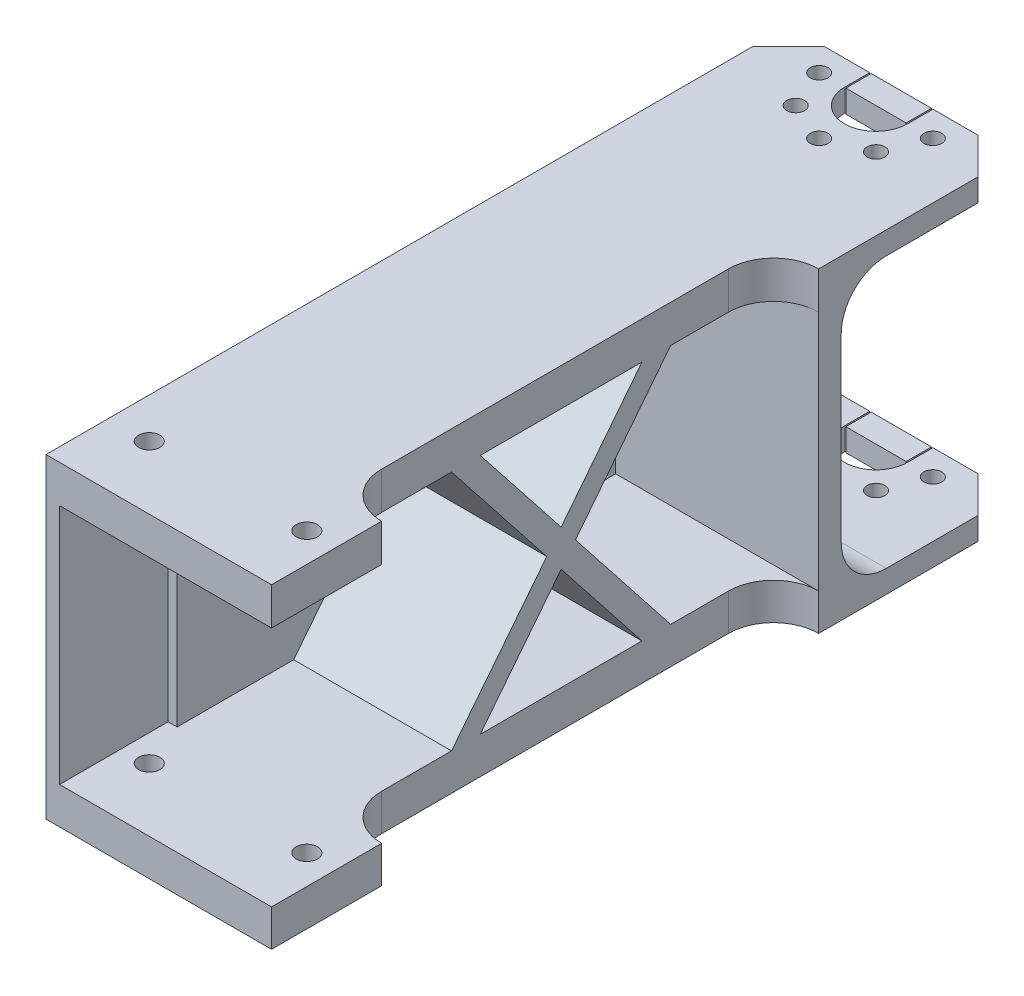
SolidWorks part; units mm, degrees
ref_plane "Front Plane" through (0, 0, 0) normal (0, 0, 1) x (1, 0, 0)
ref_plane "Top Plane" through (0, 0, 0) normal (0, 1, 0) x (1, 0, 0)
ref_plane "Right Plane" through (0, 0, 0) normal (1, 0, 0) x (0, 0, -1)
sketch "Sketch1" plane through (-21, 0, 0) normal (-1, 0, 0) x (0, 0, 1)
  line L0 (72.95, -19) -> (92.05, -19) construction
  line L1 (92.05, 19) -> (72.95, 19) construction
  line L2 (72.95, -19) -> (92.05, -19) construction
  line L3 (92.05, 19) -> (72.95, 19) construction
  line L4 (69.575, 19.1016) -> (103.275, 19.1016)
  line L5 (103.275, 19.1016) -> (103.275, -19)
  line L6 (103.275, -19) -> (69.575, -19)
  line L7 (69.575, -19) -> (69.575, -22.175)
  line L8 (69.575, -22.175) -> (106.45, -22.175)
  line L9 (106.45, -22.175) -> (106.45, 22.2766)
  line L10 (106.45, 22.2766) -> (69.575, 22.2766)
  line L11 (69.575, 22.2766) -> (69.575, 19.1016)
  line L12 (93.75, -8.4) -> (93.75, 16.6) construction
  line L13 (72.75, -15) -> (72.75, -18.8)
  line L14 (92.25, -18.8) -> (92.25, -17)
  line L15 (92.25, 19.1016) -> (72.75, 19.1016) construction
  line L16 (72.75, -15) -> (72.75, -18.8) construction
  dimension "D1" = 3.175
  dimension "D2" = 3.175
  dimension "D3" = 3.175
  dimension "D4" = 9.525
  dimension "D5" = 3.175
extrude "Boss-Extrude1" add sketch "Sketch1" along normal mid plane 31.75
sketch "Sketch2" plane through (0, 22.2766, 0) normal (0, 1, 0) x (1, 0, 0)
  circle A0 centre (-15.3431, -88.1569) radius 1.25
  circle A1 centre (-21, -90.5) radius 1.25
  circle A2 centre (-26.6569, -88.1569) radius 1.25
  circle A3 centre (-29, -82.5) radius 1.25
  circle A4 centre (-26.6569, -76.8431) radius 1.25
  circle A5 centre (-21, -74.5) radius 1.239
  circle A6 centre (-15.3431, -76.8431) radius 1.25
  circle A7 centre (-13, -82.5) radius 1.25
  dimension "D1" = 2.5
extrude "Cut-Extrude1" cut sketch "Sketch2" against normal through all both and the other way through all
sketch "Sketch4" plane through (0, 22.2766, 0) normal (0, 1, 0) x (1, 0, 0)
  circle A1 centre (-21, -82.5) radius 4.445
  dimension "D1" = 8.89
extrude "Cut-Extrude2" cut sketch "Sketch4" against normal through all both
sketch "Sketch5" plane through (-36.875, 0, 0) normal (-1, 0, 0) x (0, 0, 1)
  line L1 (106.45, 22.2766) -> (227.925, 22.2766)
  line L2 (106.45, 22.2766) -> (106.45, -22.175)
  line L3 (106.45, -22.175) -> (227.925, -22.175)
  line L4 (227.925, 22.2766) -> (227.925, -22.175)
  line L6 (224.75, 16.6) -> (224.75, -8.4) construction
  dimension "D1" = 3.175
extrude "Boss-Extrude2" add sketch "Sketch5" against normal blind 3.175
sketch "Sketch6" plane through (0, 0, 227.925) normal (0, 0, 1) x (1, 0, 0)
  line L0 (-33.7, -22.175) -> (-36.875, -22.175) construction
  line L1 (-33.7, 22.2766) -> (-11.475, 22.2766)
  line L2 (-33.7, 22.2766) -> (-33.7, 17)
  line L3 (-33.7, 17) -> (-11.475, 17)
  line L4 (-11.475, 22.2766) -> (-11.475, 17)
  line L5 (-33.7, -22.175) -> (-11.475, -22.175)
  line L6 (-33.7, -22.175) -> (-33.7, -17)
  line L7 (-33.7, -17) -> (-11.475, -17)
  line L8 (-11.475, -22.175) -> (-11.475, -17)
  line L9 (-33.7, -22.175) -> (-33.7, 22.2766) construction
  line L10 (-30.0843, -17) -> (-18, -17) construction
  line L11 (12.0843, 17) -> (-30.0843, 17) construction
  dimension "D1" = 22.225
extrude "Boss-Extrude3" add sketch "Sketch6" against normal up to surface (121.475 mm away) up to face at (-19.4125, 0.0508, 106.45)
sketch "Sketch7" plane through (0, 22.2766, 0) normal (0, 1, 0) x (1, 0, 0)
  circle A0 centre (-29, -221.5) radius 1.375
  circle A1 centre (-29, -199.5) radius 1.375
  dimension "D1" = 2.75
extrude "Cut-Extrude3" cut sketch "Sketch7" against normal through all
sketch "Sketch8" plane through (0, -22.175, 0) normal (0, -1, 0) x (1, 0, 0)
  line L0 (-11.475, 227.925) -> (-36.875, 227.925) construction
  line L1 (-21, 227.925) -> (-11.475, 227.925)
  line L2 (-21, 227.925) -> (-21, 196.175)
  line L3 (-21, 196.175) -> (-11.475, 196.175)
  line L4 (-11.475, 227.925) -> (-11.475, 196.175)
  line L5 (-11.475, 106.45) -> (-11.475, 227.925) construction
  dimension "D1" = 31.75
  dimension "D2" = 9.525
extrude "Cut-Extrude4" cut sketch "Sketch8" against normal through all
fillet "Fillet3" radius 3.81 6 edges at (-11.475, -19.5875, 196.175) (-21, -19.5875, 196.175) (-21, -19.5875, 227.925) (-21, 19.6383, 227.925) (-21, 19.6383, 196.175) (-11.475, 19.6383, 196.175)
sketch "Sketch9" plane through (-11.475, 0, 0) normal (1, 0, 0) x (0, 0, -1)
  line L1 (-151.78, -17) -> (-138.3781, 0)
  line L2 (-147.737, -17) -> (-136.3566, -2.5642)
  line L3 (-136.3566, 2.5642) -> (-147.737, 17)
  line L4 (-124.9762, -17) -> (-136.3566, -2.5642)
  line L5 (-120.9332, -17) -> (-134.3351, 0)
  line L6 (-106.45, 17) -> (-192.365, 17) construction
  line L7 (-106.45, -17) -> (-192.365, -17) construction
  line L8 (-120.9332, 17) -> (-124.9762, 17)
  line L9 (-120.9332, -17) -> (-124.9762, -17)
  line L10 (-147.737, -17) -> (-151.78, -17)
  line L11 (-147.737, 17) -> (-151.78, 17)
  line L12 (-138.3781, 0) -> (-151.78, 17)
  line L15 (-134.3351, 0) -> (-120.9332, 17)
  line L16 (-136.3566, 2.5642) -> (-124.9762, 17)
  point P2 (-132.8535, 0.2665)
  point P7 (-133.7336, -0.2418)
  dimension "D1" = 3.175
extrude "Boss-Extrude4" add sketch "Sketch9" against normal up to surface (22.225 mm away) up to face at (-33.7, 0, 167.1875)
pattern_linear "LPattern1" count 2 spacing 38.1 along (0, 0, 1) of "Boss-Extrude4"
fillet "Fillet5" radius 6.35 2 edges at (-21, -19, 103.275) (-21, 19.1016, 103.275)
sketch "Sketch11" plane through (-36.875, 0, 0) normal (-1, 0, 0) x (0, 0, 1)
  line L0 (69.575, -22.175) -> (227.925, -22.175) construction
  line L1 (227.925, 22.2766) -> (183.475, 22.2766)
  line L2 (227.925, 22.2766) -> (227.925, -22.175)
  line L3 (227.925, -22.175) -> (183.475, -22.175)
  line L4 (183.475, 22.2766) -> (183.475, -22.175)
  dimension "D1" = 44.45
extrude "Cut-Extrude6" cut sketch "Sketch11" against normal through all
sketch "Sketch12" plane through (-11.475, 0, 0) normal (1, 0, 0) x (0, 0, -1)
  line L0 (-151.78, -17) -> (-159.0332, -17) construction
  line L1 (-153.4988, -17) -> (-183.475, -17)
  line L2 (-153.4988, -17) -> (-153.4988, 17)
  line L3 (-153.4988, 17) -> (-183.475, 17)
  line L4 (-183.475, -17) -> (-183.475, 17)
extrude "Cut-Extrude7" cut sketch "Sketch12" against normal up to surface (22.225 mm away) up to face at (-33.7, 0, 155.4066)
sketch "Sketch13" plane through (-11.475, 0, 0) normal (1, 0, 0) x (0, 0, -1)
  line L0 (-151.78, -17) -> (-183.475, -17) construction
  line L1 (-183.475, -22.175) -> (-167.9685, -22.175)
  line L2 (-183.475, -22.175) -> (-183.475, -17)
  line L3 (-183.475, -17) -> (-167.9685, -17)
  line L4 (-167.9685, -22.175) -> (-167.9685, -17)
  line L5 (-151.78, 17) -> (-183.475, 17) construction
  line L6 (-183.475, 22.2766) -> (-167.9685, 22.2766)
  line L7 (-183.475, 22.2766) -> (-183.475, 17)
  line L8 (-183.475, 17) -> (-167.9685, 17)
  line L9 (-167.9685, 22.2766) -> (-167.9685, 17)
  line L11 (-171.1435, -8.4) -> (-171.1435, 16.6) construction
  dimension "D1" = 3.175
extrude "Boss-Extrude5" add sketch "Sketch13" along normal blind 6.35
sketch "Sketch14" plane through (0, 0, 183.475) normal (0, 0, 1) x (1, 0, 0)
  line L0 (-33.7, -17) -> (-5.125, -17) construction
  line L1 (-33.7, 17) -> (-34.97, 17)
  line L2 (-33.7, 17) -> (-33.7, -17)
  line L3 (-33.7, -17) -> (-34.97, -17)
  line L4 (-34.97, 17) -> (-34.97, -17)
  dimension "D1" = 1.27
extrude "Cut-Extrude8" cut sketch "Sketch14" against normal offset from surface (15.2898 mm away) 3.175
sketch "Sketch15" plane through (0, -22.175, 0) normal (0, -1, 0) x (1, 0, 0)
  circle A0 centre (-9.224, 174.4039) radius 1.5
  circle A1 centre (-31.2232, 174.5896) radius 1.5
  dimension "D1" = 3
extrude "Cut-Extrude9" cut sketch "Sketch15" against normal through all
fillet "Fillet6" radius 6.35 4 edges at (-11.475, 19.6383, 167.9685) (-11.475, 19.6383, 106.45) (-11.475, -19.5875, 106.45) (-11.475, -19.5875, 167.9685)
sketch "Sketch16" plane through (0, 22.2766, 0) normal (0, 1, 0) x (1, 0, 0)
  line L0 (-5.125, -106.45) -> (-5.125, -69.575) construction
  line L1 (-36.875, -69.575) -> (-5.125, -69.575)
  line L2 (-36.875, -69.575) -> (-36.875, -78.9355)
  line L3 (-36.875, -78.9355) -> (-25.445, -78.9355)
  line L4 (-5.125, -69.575) -> (-5.125, -78.9355)
  line L5 (-25.445, -82.5) -> (-25.445, -78.9355)
  line L6 (-16.555, -82.5) -> (-16.555, -78.9355)
  line L7 (-16.555, -78.9355) -> (-5.125, -78.9355)
  circle A0 centre (-21, -82.5) radius 4.445 construction
  arc A1 (-16.555, -82.5) -> (-25.445, -82.5) centre (-21, -82.5) ccw
extrude "Cut-Extrude13" cut sketch "Sketch16" against normal through all
chamfer "Chamfer1" distance 5.08 angle 45 4 edges at (-36.875, -20.5875, 78.9355) (-5.125, -20.5875, 78.9355) (-5.125, 20.6891, 78.9355) (-36.875, 20.6891, 78.9355)
sketch "Sketch17" plane through (0, 22.2766, 0) normal (0, 1, 0) x (1, 0, 0)
  line L0 (-31.795, -78.9355) -> (-25.445, -78.9355) construction
  line L1 (-25.245, -82.5) -> (-16.755, -82.5)
  line L2 (-25.245, -82.5) -> (-25.245, -78.9355)
  line L3 (-25.245, -78.9355) -> (-16.755, -78.9355)
  line L4 (-16.755, -82.5) -> (-16.755, -78.9355)
  line L5 (-16.555, -82.5) -> (-16.555, -78.9355) construction
  line L6 (-25.445, -78.9355) -> (-25.445, -82.5) construction
  dimension "D1" = 0.2
  dimension "D2" = 0.2
extrude "Boss-Extrude6" add sketch "Sketch17" against normal up to surface (3.175 mm away) separate body up to face at (-21, 19.1016, 91.75)
sketch "Sketch18" plane through (0, -22.175, 0) normal (0, -1, 0) x (1, 0, 0)
  line L4 (-25.245, 82.5) -> (-25.245, 78.9355)
  line L5 (-25.245, 78.9355) -> (-16.755, 78.9355)
  line L6 (-16.755, 78.9355) -> (-16.755, 82.5)
  line L7 (-16.755, 82.5) -> (-25.245, 82.5)
  line L8 (-25.245, 82.5) -> (-25.245, 78.9355)
  line L9 (-25.245, 78.9355) -> (-16.755, 78.9355)
  line L10 (-16.755, 78.9355) -> (-16.755, 82.5)
  line L11 (-16.755, 82.5) -> (-25.245, 82.5)
  dimension "D1" = 0
extrude "Boss-Extrude7" add sketch "Sketch18" against normal up to surface (3.175 mm away) separate body up to face at (-21, -19, 84.7068)
ref_plane "Plane1" through (0, 0, 164.425) normal (0, 0, 1) x (1, 0, 0)
sketch "Sketch19" plane through (0, 0, 164.425) normal (0, 0, 1) x (1, 0, 0)
  line L1 (-36.875, -22.175) -> (-34.335, -22.175)
  line L2 (-36.875, -22.175) -> (-36.875, -29.6426)
  line L3 (-36.875, -29.6426) -> (-24.175, -29.6426)
  line L4 (-24.175, -27.1026) -> (-24.175, -29.6426)
  line L7 (-24.175, -27.1026) -> (-34.335, -27.1026)
  line L8 (-34.335, -22.175) -> (-34.335, -27.1026)
  point P4 (-36.875, -25.9088)
  dimension "D1" = 7.4676
  dimension "D2" = 12.7
  dimension "D3" = 4.9276
  dimension "D4" = 2.54
extrude "Boss-Extrude8" add sketch "Sketch19" against normal blind 63.5
sketch "Sketch20" plane through (0, 0, 164.425) normal (0, 0, 1) x (1, 0, 0)
  line L0 (-24.175, -27.1026) -> (-26.5626, -24.715)
  line L1 (-26.5626, -24.715) -> (-28.9502, -27.1026)
  line L2 (-24.175, -27.1026) -> (-34.335, -27.1026) construction
  line L3 (-28.9502, -27.1026) -> (-24.175, -27.1026)
  dimension "D1" = 2.3876
extrude "Boss-Extrude9" add sketch "Sketch20" against normal up to surface (63.5 mm away) up to face at (-31.795, -26.3067, 100.925)
